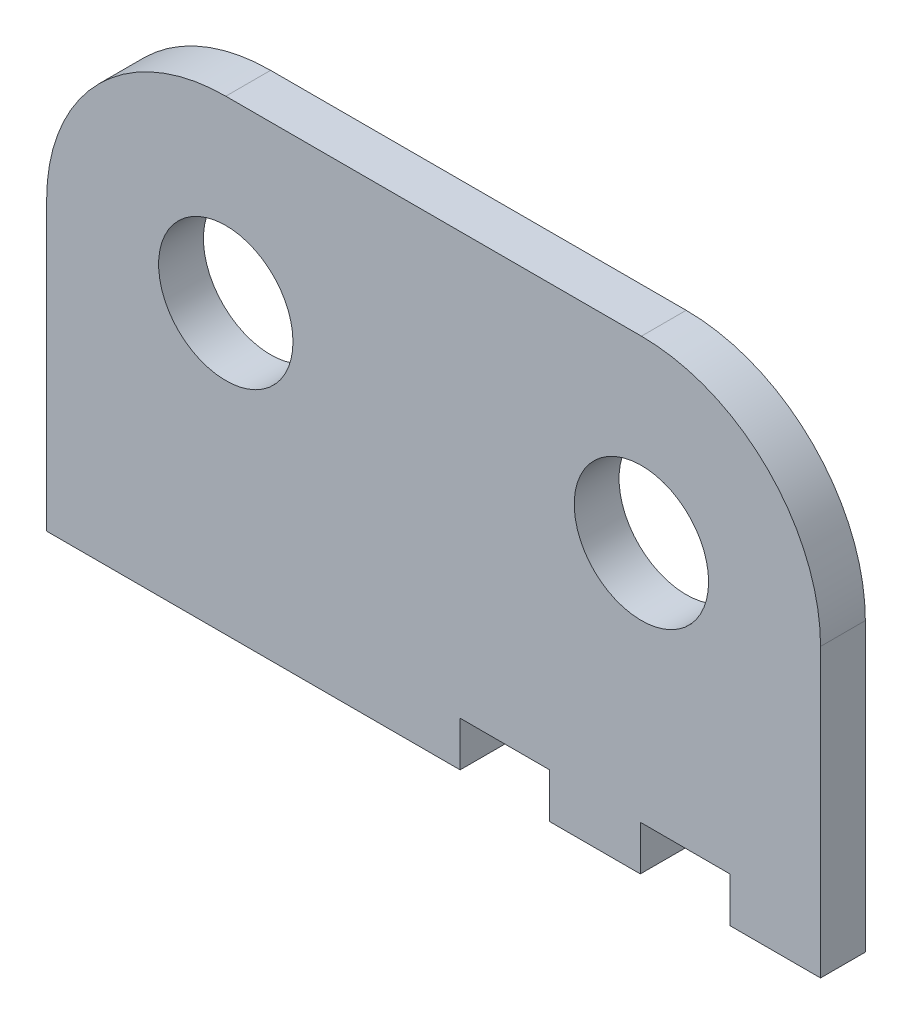
SolidWorks part; units mm, degrees
ref_plane "Front Plane" through (0, 0, 0) normal (0, 0, 1) x (1, 0, 0)
ref_plane "Top Plane" through (0, 0, 0) normal (0, 1, 0) x (1, 0, 0)
ref_plane "Right Plane" through (0, 0, 0) normal (1, 0, 0) x (0, 0, -1)
sketch "Sketch1" plane through (0, 0, 0) normal (0, 0, 1) x (1, 0, 0)
  line L0 (0, 0) -> (20.6877, 0) construction
  line L1 (20.6877, 0) -> (20.6877, 20.3568) construction
  line L2 (20.6877, 20.3568) -> (20.6877, 33.0568) construction
  line L3 (20.6877, 20.3568) -> (15.9252, 20.3568) construction
  line L4 (-8.7763, 20.3568) -> (-13.5388, 20.3568) construction
  line L8 (33.3877, 20.3568) -> (33.3877, 0)
  line L9 (-21.4763, 0) -> (33.3877, 0)
  line L10 (20.6877, 33.0568) -> (-8.7763, 33.0568)
  line L11 (-21.4763, 20.3568) -> (-21.4763, 0)
  line L12 (-4.0138, 20.3568) -> (-8.7763, 20.3568) construction
  line L13 (-21.4763, 20.3568) -> (-39.6056, 20.3568) construction
  line L14 (20.6877, 60.7428) -> (20.6877, 63.9178) construction
  circle A0 centre (20.6877, 20.3568) radius 4.7625
  circle A2 centre (-8.7763, 20.3568) radius 4.7625
  arc A6 (33.3877, 20.3568) -> (20.6877, 33.0568) centre (20.6877, 20.3568) ccw
  arc A7 (-8.7763, 33.0568) -> (-21.4763, 20.3568) centre (-8.7763, 20.3568) ccw
  dimension "D2" = 9.525
  dimension "D5" = 9.525
  dimension "D12" = 25.4
  dimension "D13" = 25.4
  dimension "D1" = 20.3568
  dimension "D3" = 43.561
  dimension "D6" = 29.464
  dimension "D8" = 30.8293
extrude "Boss-Extrude1" add sketch "Sketch1" along normal blind 3.175
sketch "Sketch2" plane through (0, 0, 0) normal (0, -1, 0) x (1, 0, 0)
  line L0 (-21.4763, 0) -> (33.3877, 0) construction
  line L1 (20.6115, 0) -> (26.9615, 0)
  line L2 (20.6115, 0) -> (20.6115, 3.175)
  line L3 (20.6115, 3.175) -> (26.9615, 3.175)
  line L4 (26.9615, 0) -> (26.9615, 3.175)
  line L5 (-21.4763, 3.175) -> (33.3877, 3.175) construction
  line L6 (33.3877, 3.175) -> (33.3877, 0) construction
  line L8 (7.8353, 3.175) -> (14.1853, 3.175)
  line L9 (7.8353, 3.175) -> (7.8353, 0)
  line L10 (7.8353, 0) -> (14.1853, 0)
  line L11 (14.1853, 3.175) -> (14.1853, 0)
  point P14 (14.1853, 1.5875)
  dimension "D1" = 6.4262
  dimension "D2" = 6.35
  dimension "D3" = 6.4262
  dimension "D4" = 6.35
extrude "Cut-Extrude1" cut sketch "Sketch2" against normal blind 3.175
